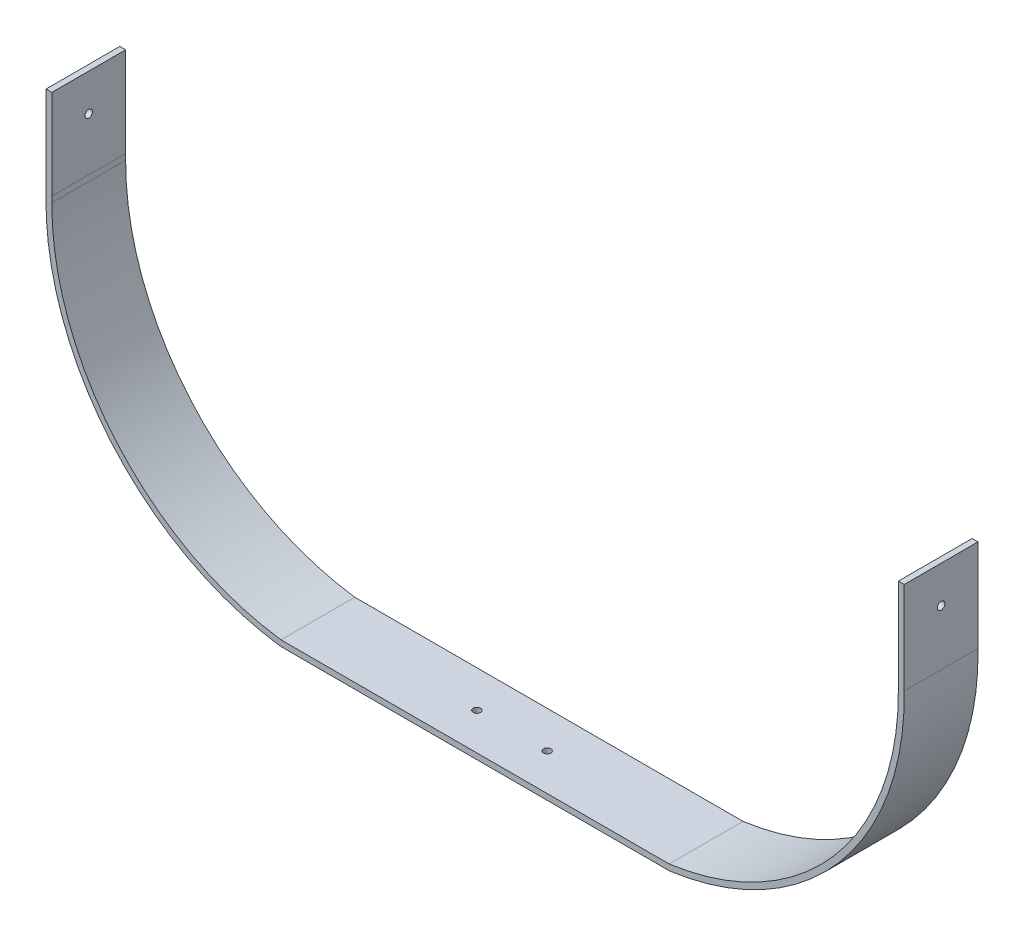
SolidWorks part; units mm, degrees
material "Thornel Mat VMA"
ref_plane "Front Plane" through (0, 0, 0) normal (0, 0, 1) x (1, 0, 0)
ref_plane "Top Plane" through (0, 0, 0) normal (0, 1, 0) x (1, 0, 0)
ref_plane "Right Plane" through (0, 0, 0) normal (1, 0, 0) x (0, 0, -1)
sketch "Sketch1" plane through (0, 0, 0) normal (0, 0, 1) x (1, 0, 0)
  line L0 (-80, 0) -> (80, 0)
  line L2 (232.5, 148) -> (232.5, 198)
  line L4 (-232.5, 148) -> (-232.5, 198)
  line L5 (-232.5, 148) -> (232.5, 148) construction
  line L6 (-232.5, 198) -> (232.5, 198) construction
  line L7 (229.325, 149.3431) -> (229.325, 198)
  line L11 (-229.325, 149.3431) -> (-229.325, 198)
  line L12 (-232.5, 198) -> (-229.325, 198)
  line L13 (229.325, 198) -> (232.5, 198)
  line L14 (80, 0) -> (232.5, 148) construction
  line L15 (78.7126, 3.175) -> (229.325, 149.3431) construction
  line L16 (-80, 0) -> (-232.5, 148) construction
  line L17 (-78.7126, 3.175) -> (-229.325, 149.3431) construction
  line L18 (-80, 0) -> (-105.4, 0)
  line L19 (-80, 3.18) -> (80, 3.18)
  line L20 (-80, 3.18) -> (-105.1852, 3.18)
  line L21 (-229.325, 149.3431) -> (-229.3406, 146.1631)
  line L22 (-229.3406, 146.1631) -> (229.325, 146.1631) construction
  line L25 (80, 0) -> (105.4, 0)
  line L26 (80, 3.18) -> (105.1852, 3.18)
  line L31 (229.325, 149.3431) -> (229.325, 146.1631)
  line L33 (-229.3406, 146.1631) -> (-229.3406, 146.1631) construction
  line L34 (-229.3406, 146.1631) -> (-229.3406, 146.1631) construction
  line L35 (-229.3406, 146.1631) -> (-229.3406, 146.1631) construction
  line L36 (-78.7126, 3.175) -> (78.7126, 3.175) construction
  arc A0 (-105.4, 0) -> (-232.5, 148) centre (-85.7667, 145.4364) cw
  arc A1 (-105.1852, 3.18) -> (-229.3406, 146.1631) centre (-85.7667, 145.4364) cw
  arc A5 (229.325, 146.1631) -> (105.1852, 3.18) centre (85.7512, 145.4343) cw
  arc A6 (105.4, 0) -> (232.5, 148) centre (85.7667, 145.4364) ccw
  point P8 (0, 0)
  dimension "D1" = 160
  dimension "D2" = 465
  dimension "D3" = 198
  dimension "D4" = 50
  dimension "D6" = 25.4
  dimension "D5" = 3.175
  dimension "D7" = 3.18
extrude "Boss-Extrude1" add sketch "Sketch1" along normal blind 40
sketch "Sketch3" plane through (0, 0, 0) normal (0, 1, 0) x (1, 0, 0)
  line L0 (-105.4, -20) -> (-19.05, -20) construction
  line L2 (-19.05, -20) -> (19.05, -20) construction
  line L3 (19.05, -20) -> (105.4, -20) construction
  line L5 (105.4, -40) -> (105.4, 0) construction
  circle A0 centre (-19.05, -20) radius 2
  circle A1 centre (19.05, -20) radius 2
  dimension "D2" = 4
  dimension "D1" = 38.1
extrude "Cut-Extrude1" cut sketch "Sketch3" along normal through all
sketch "Sketch4" plane through (-232.5, 0, 0) normal (-1, 0, 0) x (0, 0, 1)
  line L0 (20, 198) -> (20, 148) construction
  line L1 (40, 198) -> (0, 198) construction
  line L3 (0, 178) -> (40, 178) construction
  line L4 (0, 148) -> (0, 198) construction
  line L5 (40, 148) -> (40, 198) construction
  line L6 (40, 148) -> (0, 148) construction
  circle A0 centre (20, 178) radius 2.0479
  dimension "D2" = 4.0958
  dimension "D1" = 20
extrude "Cut-Extrude2" cut sketch "Sketch4" against normal through all both
